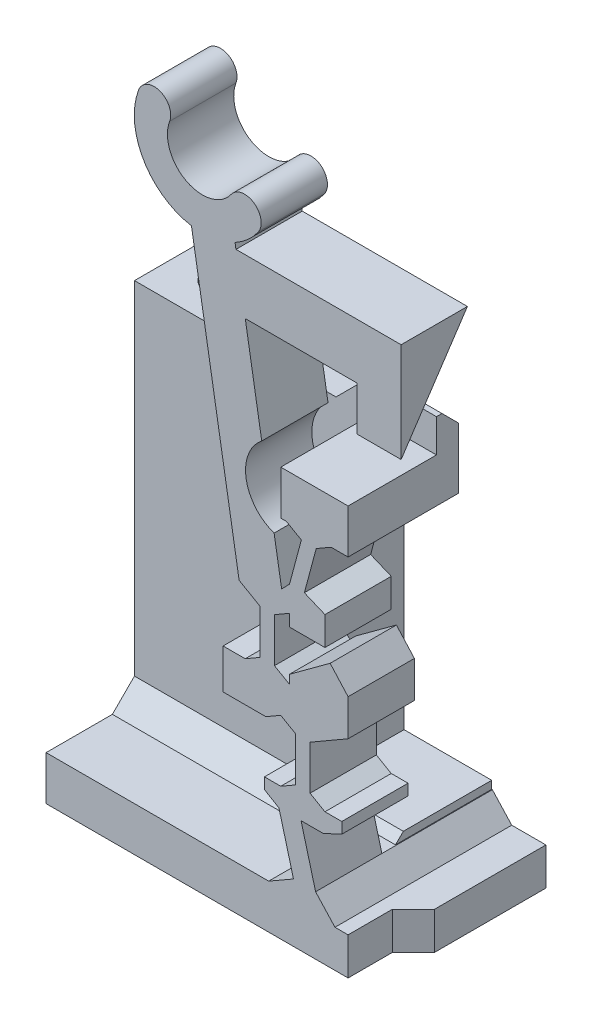
SolidWorks part; units mm, degrees
material "Nylon 6/12"
ref_plane "Front Plane" through (0, 0, 0) normal (0, 0, 1) x (1, 0, 0)
ref_plane "Top Plane" through (0, 0, 0) normal (0, 1, 0) x (1, 0, 0)
ref_plane "Right Plane" through (0, 0, 0) normal (1, 0, 0) x (0, 0, -1)
sketch "Sketch-SkeletonConfigUp" plane through (0, 0, 0) normal (0, 0, 1) x (1, 0, 0)
  line L0 (0, 0) -> (0, -50000) construction
  line L1 (0, 0) -> (4.5811, 6.2164) construction
  line L2 (9.8143, 13.3177) -> (4.5811, 13.945) construction
  line L3 (4.5811, 13.945) -> (2.9713, 10.4094) construction
  line L4 (2.9713, 10.4094) -> (4.5811, 6.2164) construction
  line L5 (4.5811, 13.945) -> (6.2429, 19.1409) construction
  line L6 (2.9713, 10.4094) -> (0.0405, 27.8193) construction
  line L7 (4.5811, 6.2164) -> (9.8143, 13.3177) construction
  line L8 (-587.3593, -797.0242) -> (9.8143, 13.3177) construction
  dimension "D2" = 7.7221
  dimension "D3" = 8.8212
  dimension "D4" = 5.2707
  dimension "D5" = 119.553
  dimension "D6" = 3.8848
  dimension "D7" = 5.4552
  dimension "D8" = 17.6549
  dimension "D9" = 4.4914
  dimension "D10" = 6.745
  dimension "D11" = 145.964
  dimension "D12" = 143.612
sketch "Sketch-SkeletonConfigDown" plane through (0, 0, 0) normal (0, 0, 1) x (1, 0, 0)
  line L0 (0, 0) -> (0, -50000) construction
  line L1 (0, 0) -> (4.5811, 6.2164) construction
  line L2 (9.8143, 13.3177) -> (4.5811, 13.945) construction
  line L3 (4.5811, 13.945) -> (6.1909, 10.4094) construction
  line L4 (6.1909, 10.4094) -> (4.5811, 6.2164) construction
  line L5 (4.5811, 13.945) -> (1.753, 18.6098) construction
  line L6 (6.1909, 10.4094) -> (-8.8652, 19.6294) construction
  line L7 (4.5811, 6.2164) -> (9.8143, 13.3177) construction
  line L8 (-589.9357, -800.5203) -> (9.8143, 13.3177) construction
  dimension "D2" = 7.7221
  dimension "D3" = 8.8212
  dimension "D4" = 5.2707
  dimension "D5" = 119.553
  dimension "D6" = 3.8848
  dimension "D7" = 5.4552
  dimension "D8" = 17.6549
  dimension "D9" = 4.4914
  dimension "D10" = 6.745
  dimension "D11" = 145.964
  dimension "D1" = 143.612
ref_plane "Plane-Cam Base" through (9.128, 0, 0) normal (1, 0, 0) x (0, 0, -1)
ref_plane "Plane-Down-to-Up Derailleur Clearance" through (6.628, 0, 0) normal (1, 0, 0) x (0, 0, -1)
ref_plane "Plane-Cam Cavity Roof" through (5.128, 0, 0) normal (1, 0, 0) x (0, 0, -1)
sketch "Sketch-SwitchBossUp" plane through (0, 0, 0) normal (0, 0, 1) x (1, 0, 0)
  line L0 (3.5811, 11.4759) -> (3.5811, 12.945) construction
  line L5 (5.5811, 12.5552) -> (5.5811, 11.263)
  line L7 (1.5115, 25.1048) -> (1.5536, 24.8548)
  line L8 (-0.4607, 24.7728) -> (1.6966, 11.9577)
  line L9 (2.9713, 10.4094) -> (0.0405, 27.8193) construction
  line L11 (0.1364, 21.2256) -> (2.1086, 21.5576) construction
  line L15 (6.628, -23.7286) -> (6.628, 23.7286) construction
  line L16 (2.9713, 10.4094) -> (4.5811, 6.2164) construction
  line L17 (3.5811, 12.945) -> (3.5811, 14.945) construction
  line L18 (5.5811, 12.945) -> (5.5811, 14.945) construction
  line L19 (4.2561, 13.945) -> (4.9061, 13.945) construction
  line L20 (3.5811, 14.945) -> (5.5811, 14.945) construction
  line L21 (3.5811, 12.945) -> (5.5811, 12.945) construction
  line L22 (4.5811, 12.945) -> (4.5811, 14.945) construction
  line L23 (4.5811, 6.2164) -> (8.5405, 7.1023) construction
  line L24 (1.9713, 9.4094) -> (1.9713, 11.4094) construction
  line L25 (3.9713, 9.4094) -> (3.9713, 11.4094) construction
  line L26 (3.9713, 9.4094) -> (1.9713, 9.4094) construction
  line L27 (1.9713, 11.4094) -> (3.9713, 11.4094) construction
  line L28 (3.5811, 7.2164) -> (5.5811, 7.2164) construction
  line L29 (3.5811, 7.2164) -> (3.5811, 5.2164) construction
  line L30 (5.5811, 7.2164) -> (5.5811, 5.2164) construction
  line L31 (3.5811, 5.2164) -> (5.5811, 5.2164) construction
  line L32 (4.9061, 6.2164) -> (4.2561, 6.2164) construction
  line L40 (3.2963, 10.4094) -> (2.6463, 10.4094) construction
  line L66 (0.0405, 27.8193) -> (0.0405, 50027.8193) construction
  line L75 (3.9992, 3.937) -> (4.6576, 1.4797) construction
  line L76 (5.5811, 11.263) -> (5.5811, 12.5552) construction
  line L77 (5.5811, 7.6061) -> (6.628, 8.2105)
  line L80 (5.8152, 10.763) -> (6.628, 9.8603)
  line L81 (9.128, 1033.2419) -> (9.128, 20.0586) construction
  line L85 (6.9307, 9.5241) -> (8.5405, 7.7363) construction
  line L88 (5.7256, 17.3347) -> (6.628, 17.3347)
  line L92 (3.7762, 8.3129) -> (6.9307, 9.5241) construction
  line L98 (1.9713, 9.0197) -> (0.9713, 9.0197)
  line L99 (0.9713, 9.0197) -> (0.9713, 7.2164)
  line L100 (0.9713, 7.2164) -> (2.9061, 7.2164)
  line L101 (4.5811, 6.2164) -> (6.9307, 9.5241) construction
  line L103 (0.0405, 27.8193) -> (1.9448, 26.4638) construction
  line L104 (6.9307, 9.5241) -> (8.5405, 7.7363) construction
  line L107 (1.9713, 9.4094) -> (1.9713, 9.0197) construction
  line L109 (0.0405, 27.8193) -> (-2.1498, 28.6358) construction
  line L111 (6.628, 9.8603) -> (6.628, 8.2105)
  line L112 (6.628, 9.8603) -> (6.9307, 9.5241) construction
  line L113 (2.8424, 4.8267) -> (2.8424, 4.3267)
  line L114 (7.3693, 7.7363) -> (7.3563, 7.7363) construction
  line L121 (5.1576, -1.1226) -> (5.1576, 1.4797) construction
  line L122 (9.028, 22.3548) -> (9.028, 20.3548)
  line L127 (5.5811, 15.3347) -> (5.5811, 14.945) construction
  line L130 (6.0345, 0.5265) -> (6.628, 0.5265)
  line L132 (2.8424, 4.3267) -> (3.4992, 3.937)
  line L133 (2.9713, 10.4094) -> (6.1909, 10.4094) construction
  line L134 (4.5811, 10.4094) -> (4.5811, 13.945) construction
  line L135 (4.5811, 10.4094) -> (4.5811, 6.2164) construction
  line L137 (3.9713, 9.4094) -> (5.5811, 7.2164) construction
  line L139 (5.8152, 10.763) -> (3.9713, 9.4094)
  line L141 (4.1576, 1.4797) -> (3.0345, 0.8347)
  line L142 (3.0345, 0.8347) -> (3.0345, -1.1653)
  line L143 (9.128, 20.0586) -> (9.128, 18.3333) construction
  line L145 (9.128, 16.6071) -> (9.128, -49992.4167) construction
  line L147 (5.5811, 11.263) -> (5.5811, 12.5552) construction
  line L150 (3.0345, -1.1653) -> (6.628, -1.1653)
  line L151 (3.4992, 3.937) -> (4.4992, 3.937) construction
  line L152 (4.5126, 14.945) -> (3.9767, 12.945)
  line L153 (5.1855, 14.945) -> (4.6496, 12.945)
  line L157 (3.5811, 17.3347) -> (3.5811, 15.3347)
  line L158 (5.8605, 15.3347) -> (6.628, 15.3347)
  line L162 (3.2963, 11.4094) -> (3.2963, 9.4094)
  line L164 (2.6463, 11.4094) -> (2.6463, 9.4094)
  line L169 (4.2561, 7.2164) -> (4.2561, 5.2164)
  line L170 (4.9061, 5.2164) -> (4.9061, 7.2164)
  line L175 (4.2561, 7.2164) -> (3.5811, 7.6061)
  line L176 (4.9061, 7.2164) -> (5.5811, 7.6061)
  line L177 (5.5811, 7.2164) -> (5.5811, 7.6061) construction
  line L179 (4.2561, 5.2164) -> (3.5811, 4.8267)
  line L180 (3.5811, 5.2164) -> (3.5811, 4.8267) construction
  line L181 (3.5811, 4.8267) -> (2.8424, 4.8267)
  line L183 (4.9061, 5.2164) -> (5.5811, 4.8267)
  line L184 (5.5811, 5.2164) -> (5.5811, 4.8267) construction
  line L186 (9.128, -23.7286) -> (9.128, 23.7286) construction
  line L187 (2.6463, 9.4094) -> (1.9713, 9.0197)
  line L188 (3.2963, 9.4094) -> (3.9713, 9.0197)
  line L189 (3.2963, 11.4094) -> (3.9713, 11.7991)
  line L190 (2.6463, 11.4094) -> (1.6966, 11.9577)
  line L191 (3.9713, 11.4094) -> (3.9713, 11.7991) construction
  line L192 (3.9713, 11.7991) -> (3.9713, 11.263)
  line L193 (4.6496, 12.945) -> (5.5811, 12.5552)
  line L194 (3.9767, 12.945) -> (3.6203, 12.5779)
  line L195 (3.9713, 11.263) -> (5.5811, 11.263)
  line L196 (3.9713, 9.4094) -> (3.9713, 9.0197)
  line L197 (3.5811, 7.2164) -> (3.5811, 7.6061) construction
  line L199 (3.5811, 7.6061) -> (2.9061, 7.2164)
  line L201 (2.8424, 4.3267) -> (2.8424, 3.937) construction
  line L202 (2.8424, 3.937) -> (3.4992, 3.937) construction
  line L205 (3.0345, 1.4797) -> (3.0345, 0.8347) construction
  line L206 (5.1576, 1.4797) -> (6.0345, 0.5265)
  line L207 (9.128, 18.3333) -> (9.128, 16.6071) construction
  line L208 (6.628, -1.1653) -> (6.628, 0.5265)
  line L209 (9.128, 20.0586) -> (9.128, 16.6071) construction
  line L211 (5.1576, 1.4797) -> (4.4992, 3.937)
  line L212 (4.1576, 1.4797) -> (3.4992, 3.937)
  line L214 (4.5126, 14.945) -> (3.8375, 15.3347)
  line L215 (3.8375, 15.3347) -> (3.5811, 15.3347)
  line L216 (5.1855, 14.945) -> (5.8605, 15.3347)
  line L217 (5.5811, 12.945) -> (5.5811, 12.5552) construction
  line L218 (5.1855, 14.945) -> (5.1855, 15.3347) construction
  line L219 (5.8605, 15.3347) -> (3.8375, 15.3347) construction
  line L221 (9.028, 22.3548) -> (9.028, 24.8548)
  line L224 (3.5811, 17.3347) -> (5.7256, 17.3347)
  line L232 (6.628, 15.3347) -> (6.628, 17.3347)
  line L236 (1.5536, 24.8548) -> (9.028, 24.8548)
  line L240 (4.4992, 3.937) -> (5.4992, 3.937)
  line L241 (5.4992, 3.937) -> (6.3424, 4.3267)
  line L248 (7.028, 22.3548) -> (1.9744, 22.3548)
  line L249 (1.9744, 22.3548) -> (2.7198, 17.9273)
  line L250 (9.028, 20.3548) -> (7.028, 20.3548)
  line L251 (7.028, 20.3548) -> (7.028, 22.3548)
  line L252 (3.2801, 14.5986) -> (3.6203, 12.5779)
  line L253 (4.2672, 14.0291) -> (4.895, 13.8608) construction
  line L254 (5.1576, 1.4797) -> (4.1576, 1.4797) construction
  line L255 (4.1576, 1.4797) -> (3.0345, 1.4797) construction
  line L367 (5.5811, 4.8267) -> (6.3424, 4.8267)
  line L368 (6.3424, 4.8267) -> (6.3424, 4.3267)
  arc A0 (1.5115, 25.1048) -> (2.5558, 26.0289) centre (0.0405, 27.8193) ccw
  arc A1 (-0.4607, 24.7728) -> (-2.8525, 28.8978) centre (0.0405, 27.8193) cw
  arc A2 (-2.8525, 28.8978) -> (-1.447, 28.3738) centre (-2.1498, 28.6358) cw
  arc A3 (2.5558, 26.0289) -> (1.3338, 26.8987) centre (1.9448, 26.4638) ccw
  arc A4 (-1.447, 28.3738) -> (1.3338, 26.8987) centre (0.0405, 27.8193) ccw
  arc A5 (3.5811, 12.945) -> (3.5811, 14.945) centre (3.1778, 13.945) ccw construction
  arc A6 (5.5811, 12.945) -> (5.5811, 14.945) centre (5.9843, 13.945) cw construction
  arc A7 (2.5293, 9.921) -> (1.9713, 11.4094) centre (1.568, 10.4094) ccw construction
  arc A8 (3.9713, 11.4094) -> (3.9713, 9.4094) centre (4.3745, 10.4094) ccw construction
  arc A9 (3.5811, 7.2164) -> (3.5811, 5.2164) centre (3.1779, 6.2164) cw construction
  arc A10 (5.5811, 7.2164) -> (5.5811, 5.2164) centre (5.9844, 6.2164) ccw construction
  circle A28 centre (0.0405, 27.8193) radius 2.3375 construction
  arc A29 (1.9713, 9.4094) -> (2.5293, 9.921) centre (1.568, 10.4094) ccw construction
  arc A30 (3.2801, 14.5986) -> (2.7198, 17.9273) centre (3.9114, 16.4164) cw
  point P53 (4.5811, 13.945)
  point P63 (2.9713, 10.4094)
  point P93 (1.1225, 21.3916)
  dimension "D23" = 1.5875
  dimension "D24" = 0.75
  dimension "D2" = 2
  dimension "D5" = 2
  dimension "D8" = 42
  dimension "D16" = 42
  dimension "D27" = 120
  dimension "D28" = 120
  dimension "D29" = 120
  dimension "D30" = 120
  dimension "D31" = 120
  dimension "D32" = 120
  dimension "D33" = 120
  dimension "D34" = 120
  dimension "D17" = 0.5
  dimension "D21" = 2
  dimension "D38" = 2
  dimension "D39" = 0.5
  dimension "D40" = 60
  dimension "D41" = 1
  dimension "D42" = 45
  dimension "D43" = 120
  dimension "D10" = 15
  dimension "D25" = 15
  dimension "D26" = 120
  dimension "D35" = 120
  dimension "D20" = 3
  dimension "D48" = 2
  dimension "D82" = 1
  dimension "D83" = 3.5
  dimension "D14" = 2.5
  dimension "D15" = 0.25
  dimension "D7" = 2
  dimension "D9" = 2
  dimension "D6" = 0.65
  dimension "D12" = 1
extrude "Boss-Switch Body" add sketch "Sketch-SwitchBossUp" along normal blind 3
sketch "Sketch1" plane through (0, 0, 0) normal (0, 0, -1) x (-1, 0, 0)
  line L1 (-7.5811, -1.1653) -> (0.4122, -1.1653)
  line L2 (-7.5811, -1.1653) -> (-7.5811, 0.5265)
  line L4 (0.4122, -1.1653) -> (0.4122, 0.8347)
  line L5 (-3.5811, 18.8347) -> (-7.5811, 18.8347)
  line L10 (-7.5811, 18.8347) -> (-7.5811, 15.3347)
  line L11 (-4.1576, 1.4797) -> (-5.1576, 1.4797)
  line L12 (-7.5811, 15.3347) -> (-3.5811, 15.3347)
  line L13 (-4.1576, 1.4797) -> (-3.0345, 0.8347)
  line L14 (-3.5811, 15.3347) -> (-3.5811, 18.8347)
  line L20 (-4.4992, 3.937) -> (-5.1576, 1.4797) construction
  line L22 (-3.0345, -1.1653) -> (-6.628, -1.1653) construction
  line L23 (-3.0345, 0.8347) -> (0.4122, 0.8347)
  line L24 (-5.1576, 1.4797) -> (-6.0345, 0.5265)
  line L25 (-6.0345, 0.5265) -> (-7.5811, 0.5265)
  dimension "D1" = 3.5
extrude "Boss-Flange Width" add sketch "Sketch1" along normal blind 5
ref_plane "Plane-Sta2Sit Groove" through (0.0405, 0, 0) normal (1, 0, 0) x (0, 0, -1)
ref_plane "Plane-Cam Outer Surface" through (-12.0395, 0, 0) normal (1, 0, 0) x (0, 0, -1)
ref_plane "Plane-FlangeTop" through (-7.0395, 0, 0) normal (1, 0, 0) x (0, 0, -1)
sketch "Sketch2" plane through (-7.0395, 0, 0) normal (1, 0, 0) x (0, 0, -1)
  line L0 (5, 15.3347) -> (-3, 15.3347) construction
  line L1 (5, 17.3347) -> (1, 17.3347)
  line L2 (5, 17.3347) -> (5, 15.3347)
  line L3 (5, 15.3347) -> (1, 15.3347)
  line L4 (1, 17.3347) -> (1, 15.3347)
  line L5 (-3, -1.1653) -> (-3, 0.5265) construction
  line L11 (5, 0.8347) -> (-3, 0.8347)
  line L12 (5, 0.8347) -> (5, -1.1653)
  line L13 (5, -1.1653) -> (-3, -1.1653)
  line L14 (-3, 0.8347) -> (-3, -1.1653)
  line L15 (0, 10.4094) -> (0, 27.8193) construction
  line L17 (5, 0.5265) -> (5, -1.1653) construction
  line L18 (-3, 0.8347) -> (0, 0.8347) construction
  dimension "D1" = 1
  dimension "D2" = 2
extrude "Boss-Flange Height" add sketch "Sketch2" along normal up to surface (11.6675 mm away)
sketch "Sketch10" plane through (0, 15.3347, 0) normal (0, 1, 0) x (1, 0, 0)
  line L0 (9.128, -23.7286) -> (9.128, 23.7286) construction
  line L1 (7.5811, 5) -> (5.128, 5)
  line L2 (7.5811, 5) -> (7.5811, 2)
  line L3 (7.5811, 2) -> (5.128, 2)
  line L5 (4.628, 7) -> (4.628, 1) construction
  line L6 (3.5811, 1) -> (-7.0395, 1) construction
  line L8 (5.128, 5) -> (5.128, 2)
  dimension "D1" = 1
  dimension "D2" = 0.5
  dimension "D3" = 4.5
extrude "Cut-Up-To-Down Derailleur Clearance" cut sketch "Sketch10" along normal up to next
sketch "Sketch17" plane through (0, 15.3347, 0) normal (0, -1, 0) x (1, 0, 0)
  line L0 (5.128, -5) -> (-7.0395, -5)
  line L1 (5.128, -5) -> (-7.0395, -5) construction
  line L2 (-7.0395, -5) -> (-7.0395, -1)
  line L3 (-7.0395, -1) -> (5.128, -1)
  line L4 (5.128, -1) -> (5.128, -5)
  line L5 (-7.0395, -1) -> (-7.0395, -5) construction
extrude "Boss-Flange Support" add sketch "Sketch17" along normal up to surface (14.5 mm away) up to face at (-2.0025, 0.8347, -1)
sketch "Sketch-HolePositions" plane through (0, -1.1653, 0) normal (0, -1, 0) x (1, 0, 0)
  line L0 (-7.0395, -3) -> (7.5811, -3) construction
  line L1 (7.5811, -5) -> (-7.0395, -5) construction
  line L2 (7.5811, -5) -> (7.5811, 0) construction
  line L4 (-7.0395, -22.2167) -> (-7.0395, 22.2167) construction
  point P6 (-5.0395, -3)
  point P7 (-0.5395, -3)
  dimension "D1" = 2
  dimension "D2" = 4.5
  dimension "D3" = 2
sketch "Sketch6" plane through (0, -1.1653, 0) normal (0, -1, 0) x (-1, 0, 0)
  point P0 (5.0395, 3)
  point P3 (0.5395, 3)
hole_wizard "Tap Drill for M2x0.4 Tap1" positions "Sketch6" profile "Sketch5" hole size "M2x0.4" standard "ANSI Metric" end condition through all
sketch "Sketch5" plane through (-5.0395, -1.1653, -3) normal (1, 0, 0) x (0, 0, -1)
  line L0 (0, 0) -> (0, 30.5511)
  line L1 (0, 30.5511) -> (0.8, 30.5511)
  line L2 (0.8, 30.5511) -> (0.8, 0)
  line L5 (0.8, 0) -> (0, 0)
  line L11 (0, -6.35) -> (0, 107.95) construction
  dimension "Thru Hole Dia." = 1.6
  dimension "Thru Hole Depth" = 30.5511
sketch "Sketch9" plane through (0, -1.1653, 0) normal (0, -1, 0) x (1, 0, 0)
  point P0 (-5.0395, -3)
  point P3 (-0.5395, -3)
hole_wizard "M2 Clearance Hole2" positions "Sketch9" profile "Sketch8" hole size "M2" standard "ANSI Metric"
sketch "Sketch8" plane through (-5.0395, -1.1653, -3) normal (1, 0, 0) x (0, 0, -1)
  line L0 (0, 0) -> (0, 15.721)
  line L1 (0, 15.721) -> (1.2, 15)
  line L2 (1.2, 15) -> (1.2, 0)
  line L5 (1.2, 0) -> (0, 0)
  line L10 (0, 15.721) -> (-1.2, 15) construction
  line L11 (0, -6.35) -> (0, 107.95) construction
  dimension "Hole Dia." = 2.4
  dimension "Hole Depth" = 15
  dimension "Drill Angle" = 118
sketch "Sketch-Measurements for Derailleur Ramps" [suppressed] plane through (0, 0, 0) normal (0, 0, 1) x (1, 0, 0)
  line L0 (3.184, 15.1695) -> (2.4687, 19.4188)
  line L1 (2.8264, 17.2941) -> (1.8402, 17.1281)
  line L2 (2.9713, 10.4094) -> (0.0405, 27.8193) construction
  line L3 (1.8402, 17.1281) -> (-1.3081, 15.0016)
  line L4 (6.1909, 10.4094) -> (-8.8652, 19.6294) construction
  line L5 (1.8402, 17.1281) -> (2.6012, 12.6077)
  line L6 (2.6012, 12.6077) -> (-1.3081, 15.0016)
  line L7 (0.2661, 16.0649) -> (0.2661, 17.1281)
  line L8 (0.2661, 17.1281) -> (1.8402, 17.1281)
  line L9 (6.1909, 10.4094) -> (2.9713, 10.4094)
  line L10 (5.386, 8.3129) -> (3.7762, 8.3129)
  line L11 (2.6116, 18.5698) -> (1.5115, 25.1048) construction
  line L12 (6.1909, 10.4094) -> (4.5811, 6.2164) construction
  line L13 (4.5811, 8.3129) -> (4.5811, 8.7912)
  line L14 (4.5811, 6.2164) -> (5.386, 8.3129)
  line L15 (2.9713, 10.4094) -> (4.5811, 6.2164) construction
  line L16 (3.7762, 8.3129) -> (4.5811, 6.2164)
  line L17 (5.386, 8.3129) -> (5.386, 8.7912)
  dimension "D1" = 1.5742
  dimension "D2" = 0.8049
ref_plane "Plane1" through (0, 7.1023, 0) normal (0, 1, 0) x (1, 0, 0)
ref_plane "Plane-Cantilever Cut" [suppressed] through (7.0848, 8.5204, -1.9058) normal (-0.6301, -0.7578, 0.1695) x (-0.7765, 0.6151, -0.1368)
sketch "Sketch14" [suppressed] plane through (7.0848, 8.5204, -1.9058) normal (-0.6301, -0.7578, 0.1695) x (-0.7765, 0.6151, -0.1368)
  line L0 (2.3023, -1.6911) -> (-0.3551, -1.6911)
  line L2 (2.3023, -4.3362) -> (2.3023, -1.6911)
  line L3 (-0.3551, -1.6911) -> (-0.3551, -4.4608)
  line L5 (-0.3551, -4.4608) -> (1.0087, -5.0843)
  line L6 (1.0087, -5.0843) -> (2.3023, -4.3362)
extrude "Cut-Down-to-Up Cantilever Slope" [suppressed] cut sketch "Sketch14" against normal up to next
ref_plane "Plane-Symmetry Plane" through (0, 0, 1.5) normal (0, 0, 1) x (1, 0, 0)
sketch "Sketch-Cable Center Point" plane through (0, 0, 1.5) normal (0, 0, 1) x (1, 0, 0)
  line L0 (0.0405, 27.8193) -> (0.1722, 27.0366)
  line L1 (2.9713, 10.4094) -> (0.0405, 27.8193) construction
  point P0 (0.0405, 27.8193)
  dimension "D1" = 0.7937
chamfer "Chamfer-Flange Support" distance 1.5 angle 45 1 edges at (3.5811, 17.3347, -3)
chamfer "Chamfer-Flange Support 2" distance 1.5 angle 45 2 edges at (5.128, 17.0847, -2) (5.128, 15.3347, -1.5)
chamfer "Chamfer-Flange Support 3" distance 1 angle 45 1 edges at (-2.0025, 0.8347, -1)
chamfer "Chamfer7" [suppressed] distance 1 angle 45
sketch "Sketch23" plane through (0, 0, -1) normal (0, 0, 1) x (1, 0, 0)
  line L0 (5.128, 1.8347) -> (1.1605, 1.8347)
  line L1 (-7.0395, 1.8347) -> (5.128, 1.8347) construction
  line L2 (1.1605, 1.8347) -> (1.1605, 13.8347)
  line L3 (1.1605, 13.8347) -> (5.128, 13.8347)
  line L4 (5.128, 13.8347) -> (5.128, 1.8347)
  line L5 (0.6605, -1.1653) -> (0.6605, 13.8347) construction
  dimension "D1" = 0.5
extrude "Cut-Gap for Printing" cut sketch "Sketch23" against normal through all
sketch "Sketch25" plane through (0, 0, 0) normal (0, 0, 1) x (1, 0, 0)
  line L0 (6.628, 15.3347) -> (7.5811, 15.3347)
  line L1 (7.5811, 15.3347) -> (7.5811, 18.8347)
  line L2 (7.5811, 18.8347) -> (6.628, 18.8347)
  line L3 (6.628, -23.7286) -> (6.628, 23.7286) construction
  line L4 (7.5811, 18.8347) -> (3.5811, 18.8347) construction
  line L5 (6.628, 18.8347) -> (6.628, 15.3347)
  line L6 (7.5811, 18.8347) -> (7.5811, 15.3347) construction
extrude "Cut-Derailleur Clearance" cut sketch "Sketch25" against normal through all
chamfer "Chamfer8" distance 1 angle 45 1 edges at (6.628, -0.3194, 0)
ref_plane "Plane2" through (-3.0866, 5.589, 8.3835) normal (0.2929, -0.5304, -0.7956) x (-0.9561, -0.1625, -0.2437)
sketch "Sketch26" plane through (-3.0866, 5.589, 8.3835) normal (0.2929, -0.5304, -0.7956) x (-0.9561, -0.1625, -0.2437)
  line L0 (-7.553, 20.6804) -> (-7.553, 14.9094)
  line L1 (-12.6703, 20.6804) -> (-5.5238, 20.6804) construction
  line L3 (-7.553, 14.9094) -> (-20.0302, 14.9094)
  line L4 (-20.0302, 14.9094) -> (-20.0302, 20.6804)
  line L5 (-20.0302, 20.6804) -> (-7.553, 20.6804)
extrude "Cut-Up-to-Down Cantilever Slope" cut sketch "Sketch26" along normal up to next
sketch "Sketch27" plane through (5.128, 0, 0) normal (1, 0, 0) x (0, 0, -1)
  line L0 (3.5, 18.8347) -> (3.5, 13.8347) construction
  line L1 (2.5, 18.8347) -> (5, 18.8347)
  line L2 (2.5, 18.8347) -> (2.5, 13.8347)
  line L3 (2.5, 13.8347) -> (5, 13.8347)
  line L4 (5, 18.8347) -> (5, 13.8347)
  dimension "D1" = 1
extrude "Cut-Wide Derailleur Clearance" cut sketch "Sketch27" against normal blind 4 and the other way through all
chamfer "Chamfer9" distance 1.25 angle 45 1 edges at (4.8545, 18.8347, -2.5)
sketch "Sketch28" plane through (0, 0, -1) normal (0, 0, 1) x (1, 0, 0)
  line L0 (3.5811, 18.8347) -> (6.628, 18.8347)
  line L1 (6.628, 18.8347) -> (6.628, 17.3347)
  line L2 (6.628, 17.3347) -> (3.5811, 17.3347)
  line L3 (3.5811, 17.3347) -> (3.5811, 18.8347)
extrude "Cut-Extrude1" cut sketch "Sketch28" along normal up to surface (1 mm away) up to face at (5.1045, 18.0847, 0)
equation "\"axle-diameter\"=2"
equation "\"switch-thickness\"=12"
equation "\"base-width\"=4.0"
equation "\"axle-bushing-radius\"=3"
equation "\"clearance\"= 0.25"
equation "\"arm-width\"=1.5"
equation "\"min-diameter\"=70"
equation "\"alpha\"=143.6120"
equation "\"gamma\"=119.5526"
equation "\"delta\"=145.9637"
equation "\"epsilon\"=6.7452"
equation "\"l_AB\"=8.8212"
equation "\"l_AC\"=4.4914"
equation "\"l_BD\"=5.2707"
equation "\"l_CD\"=3.8848"
equation "\"l_CE\"=17.6549"
equation "\"l_DF\"=5.4552"
equation "\"l_OA\"=7.7221"
equation "\"D2@Sketch-SkeletonConfigUp\" = \"l_OA\""
equation "\"D3@Sketch-SkeletonConfigUp\" = \"l_AB\""
equation "\"D4@Sketch-SkeletonConfigUp\" = \"l_BD\""
equation "\"D5@Sketch-SkeletonConfigUp\" = \"gamma\""
equation "\"D6@Sketch-SkeletonConfigUp\" = \"l_CD\""
equation "\"D7@Sketch-SkeletonConfigUp\" = \"l_DF\""
equation "\"D8@Sketch-SkeletonConfigUp\" = \"l_CE\""
equation "\"D9@Sketch-SkeletonConfigUp\" = \"l_AC\""
equation "\"D_groove\"=3.175"
equation "\"D7@Sketch-SkeletonConfigDown\" = \"l_DF\""
equation "\"D6@Sketch-SkeletonConfigDown\" = \"l_CD\""
equation "\"D2@Sketch-SkeletonConfigDown\" = \"l_OA\""
equation "\"D3@Sketch-SkeletonConfigDown\" = \"l_AB\""
equation "\"D9@Sketch-SkeletonConfigDown\" = \"l_AC\""
equation "\"D8@Sketch-SkeletonConfigDown\" = \"l_CE\""
equation "\"D5@Sketch-SkeletonConfigDown\" = \"gamma\""
equation "\"D4@Sketch-SkeletonConfigDown\" = \"l_BD\""
equation "\"D1@Sketch-SkeletonConfigDown\" = \"alpha\""
equation "\"hinge_length\"=1.5"
equation "\"hinge_depth\"=0.25"
equation "\"D10@Sketch-SkeletonConfigUp\"=\"epsilon\""
equation "\"D11@Sketch-SkeletonConfigUp\"=\"delta\""
equation "\"D12@Sketch-SkeletonConfigUp\"=\"alpha\""
equation "\"D11@Sketch-SkeletonConfigDown\"=\"delta\""
equation "\"D10@Sketch-SkeletonConfigDown\"=\"epsilon\""
equation "\"EE_dx\"=8.9056"
equation "\"EE_dy\"=8.1898"
equation "\"r_groove\"=\"D_groove\"/2"
equation "\"t_wall\"=25.4/16"
equation "\"width_lower\"=\"D_groove\"+\"t_wall\""
equation "\"cable_to_bottom\"=30.6257"
equation "\"switch_EE-up_base_dy\"=24"
equation "\"switch_EE-down_base_dy\"=16"
equation "\"D_axle\"=25.4/8"
equation "\"D_up_to_down\"=16"
equation "\"D_down_to_up\"=25"
equation "\"t_cam_base\"=7.5"
equation "\"D23@Sketch-SwitchBossUp\"=\"D_groove\"/2"
equation "\"D1@Sketch-Cable Center Point\"=\"D_groove\"/4"
